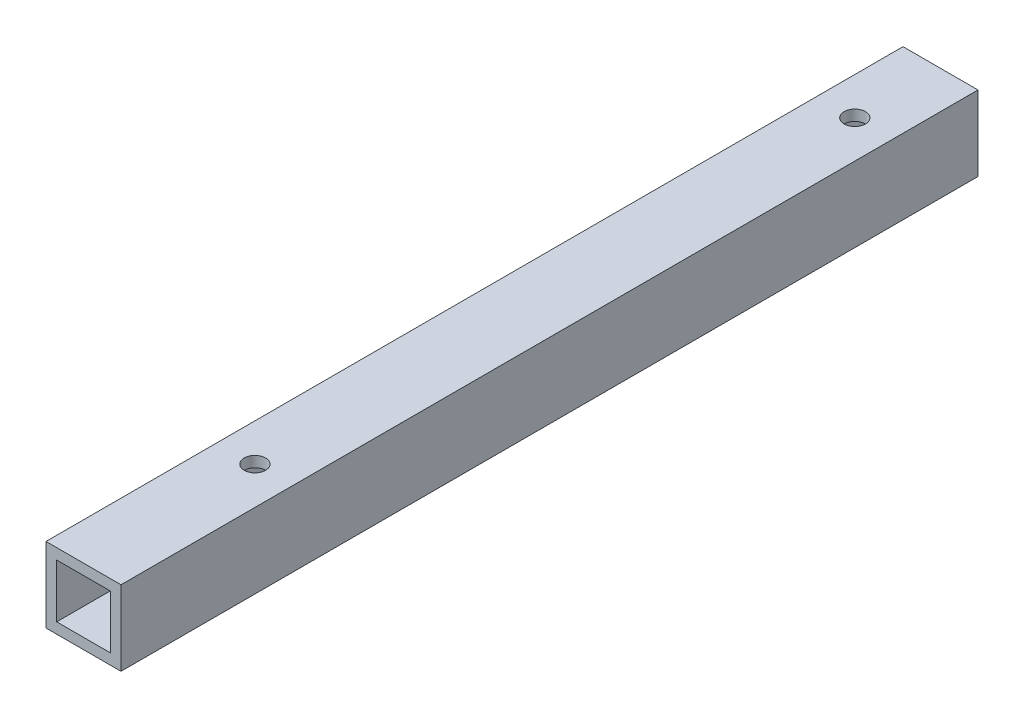
SolidWorks part; units mm, degrees
ref_plane "Front Plane" through (0, 0, 0) normal (0, 0, 1) x (1, 0, 0)
ref_plane "Top Plane" through (0, 0, 0) normal (0, 1, 0) x (1, 0, 0)
ref_plane "Right Plane" through (0, 0, 0) normal (1, 0, 0) x (0, 0, -1)
sketch "Sketch1" plane through (0, 0, 0) normal (0, 0, 1) x (1, 0, 0)
  line L1 (0, 0) -> (22.225, 0)
  line L2 (0, 0) -> (0, 22.225)
  line L3 (0, 22.225) -> (22.225, 22.225)
  line L4 (22.225, 0) -> (22.225, 22.225)
  dimension "D1" = 22.225
  dimension "D2" = 22.225
extrude "Boss-Extrude2" add sketch "Sketch1" along normal blind 254 contours L3 L4 L1 L2
sketch "Sketch2" plane through (0, 0, 0) normal (0, 0, -1) x (-1, 0, 0)
  line L0 (-19.05, 19.05) -> (-3.175, 19.05)
  line L1 (-19.05, 19.05) -> (-19.05, 3.175)
  line L2 (-19.05, 3.175) -> (-3.175, 3.175)
  line L3 (-3.175, 19.05) -> (-3.175, 3.175)
  line L4 (0, 0) -> (0, 22.225) construction
  line L5 (0, 0) -> (-22.225, 0) construction
  line L6 (0, 22.225) -> (-22.225, 22.225) construction
  line L7 (-22.225, 0) -> (-22.225, 22.225) construction
  dimension "D1" = 3.175
  dimension "D2" = 3.175
  dimension "D3" = 3.175
  dimension "D4" = 3.175
extrude "Cut-Extrude1" cut sketch "Sketch2" against normal through all
sketch "Sketch3" plane through (0, 22.225, 0) normal (0, 1, 0) x (1, 0, 0)
  line L0 (0, 0) -> (22.225, 0) construction
  line L1 (0, -254) -> (22.225, -254) construction
  circle A0 centre (11.1125, -25.4) radius 3.175
  circle A1 centre (11.1125, -203.2) radius 3.175
  dimension "D1" = 6.35
  dimension "D2" = 25.4
  dimension "D3" = 6.35
  dimension "D4" = 50.8
extrude "Cut-Extrude2" cut sketch "Sketch3" against normal through all
